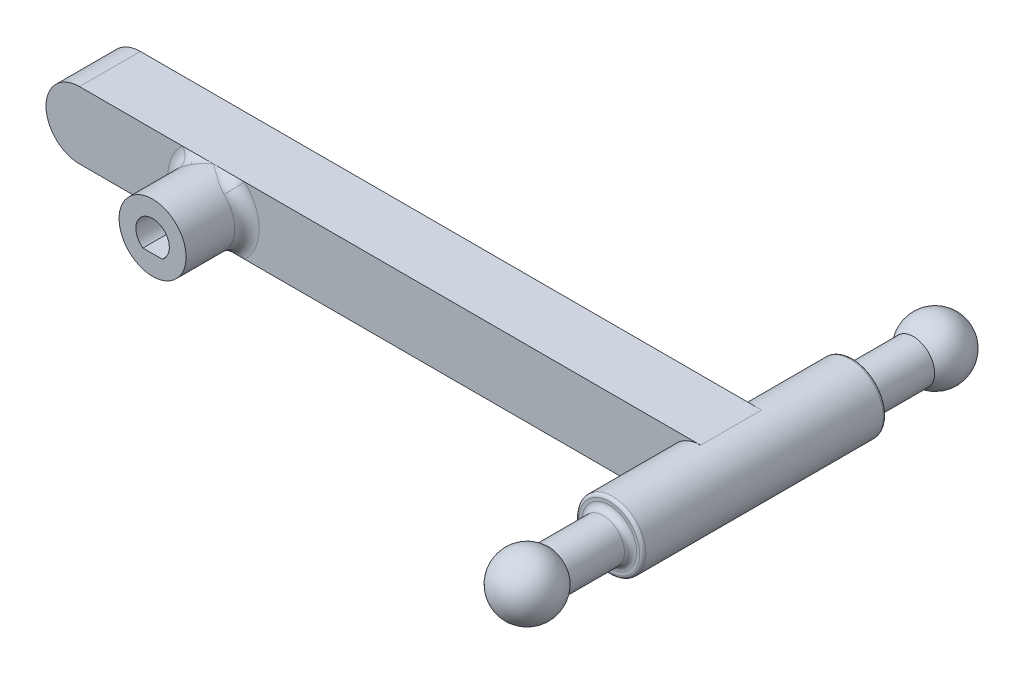
SolidWorks part; units mm, degrees
ref_plane "Front Plane" through (0, 0, 0) normal (0, 0, 1) x (1, 0, 0)
ref_plane "Top Plane" through (0, 0, 0) normal (0, 1, 0) x (1, 0, 0)
ref_plane "Right Plane" through (0, 0, 0) normal (1, 0, 0) x (0, 0, -1)
sketch "Sketch2" plane through (0, 0, 0) normal (0, 0, 1) x (1, 0, 0)
  line L0 (80, 0) -> (-42.1921, 0) construction
  line L2 (-22, -5.5) -> (80, -5.5)
  line L3 (80, -5.5) -> (80, 5.5)
  line L4 (0, 24.5757) -> (0, -40.5685) construction
  line L6 (-22, 5.5) -> (80, 5.5)
  line L7 (-1.5811, -2.25) -> (1.5811, -2.25)
  arc A0 (-22, 5.5) -> (-22, -5.5) centre (-22, 0) ccw
  arc A3 (1.5811, -2.25) -> (-1.5811, -2.25) centre (0, 0) ccw
  point P14 (0, 2.75)
  dimension "D1" = 5.5
  dimension "D5" = 2.75
  dimension "D2" = 80
  dimension "D3" = 22
  dimension "D4" = 5
extrude "Boss-Extrude2" add sketch "Sketch2" along normal mid plane 10
sketch "Sketch3" plane through (80, 0, 0) normal (1, 0, 0) x (0, 0, -1)
  line L0 (33.5, 0) -> (-33.5, 0) construction
  line L1 (-33.5, 0) -> (-33.5, 3.5)
  line L2 (-33.5, 3.5) -> (-21, 3.5)
  line L3 (-20, 4.5) -> (-20, 5)
  line L4 (-19.5, 5.5) -> (19.5, 5.5)
  line L5 (20, 5) -> (20, 4.5)
  line L6 (21, 3.5) -> (33.5, 3.5)
  line L7 (33.5, 3.5) -> (33.5, 0)
  line L8 (33.5, 0) -> (-33.5, 0)
  arc A0 (-21, 3.5) -> (-20, 4.5) centre (-21, 4.5) ccw
  arc A1 (20, 4.5) -> (21, 3.5) centre (21, 4.5) ccw
  arc A2 (-20, 5) -> (-19.5, 5.5) centre (-19.5, 5) cw
  arc A3 (19.5, 5.5) -> (20, 5) centre (19.5, 5) cw
  point P12 (20, 4.75)
  point P13 (0, 5.5)
  point P17 (-20, 5.5)
  point P20 (20, 5.5)
  dimension "D7" = 1
  dimension "D8" = 1
  dimension "D9" = 0.5
  dimension "D10" = 0.5
  dimension "D1" = 40
  dimension "D2" = 13.5
  dimension "D3" = 13.5
  dimension "D4" = 3.5
  dimension "D5" = 5.5
  dimension "D6" = 3.5
revolve "Revolve12" add sketch "Sketch3" angle 360 about L0
sketch "Sketch5" plane through (0, 0, -33.5) normal (0, 0, -1) x (-1, 0, 0)
  line L0 (-80, 5) -> (-80, -5) construction
  line L1 (-80, 5) -> (-80, -5)
  circle A0 centre (-80, 0) radius 5 construction
  arc A1 (-80, 5) -> (-80, -5) centre (-80, 0) ccw
revolve "Revolve16" add sketch "Sketch5" angle 360 about L0
sketch "Sketch6" plane through (0, 0, 33.5) normal (0, 0, 1) x (1, 0, 0)
  line L0 (80, 5) -> (80, -5) construction
  line L1 (80, 5) -> (80, -5)
  circle A0 centre (80, 0) radius 5 construction
  arc A1 (80, 5) -> (80, -5) centre (80, 0) ccw
revolve "Revolve17" add sketch "Sketch6" angle 360 about L0
sketch "Sketch8" plane through (0, 0, 5) normal (0, 0, 1) x (1, 0, 0)
  line L0 (-1.5811, -2.25) -> (1.5811, -2.25)
  circle A0 centre (0, 0) radius 5.5
  arc A1 (1.5811, -2.25) -> (-1.5811, -2.25) centre (0, 0) ccw
  point P6 (0, 2.75)
  dimension "D1" = 2.75
  dimension "D2" = 2.75
  dimension "D3" = 5
extrude "Boss-Extrude5" add sketch "Sketch8" along normal mid plane 20
fillet "Fillet1" radius 2 2 edges at (-5.5, 0, 5) (5.5, 0, 5)
sketch "Sketch9" plane through (0, -2.25, 0) normal (0, 1, 0) x (1, 0, 0)
  line L0 (0, -15) -> (0, -5) construction
  line L1 (-5.5, -15) -> (5.5, -15) construction
  circle A0 centre (0, -10) radius 1.5
  dimension "D1" = 3
extrude "Cut-Extrude1" cut sketch "Sketch9" against normal blind 10
sketch "Sketch10" plane through (0, 5.5, 0) normal (0, 1, 0) x (1, 0, 0)
  line L0 (84.5, 20) -> (75.5, 20) construction
  line L1 (100.096, 40.1532) -> (53.8183, 40.1532)
  line L2 (100.096, 40.1532) -> (100.096, 20)
  line L3 (100.096, 20) -> (53.8183, 20)
  line L4 (53.8183, 40.1532) -> (53.8183, 20)
  line L5 (114.0912, -20) -> (54.9379, -20)
  line L6 (114.0912, -20) -> (114.0912, -45.1915)
  line L7 (114.0912, -45.1915) -> (54.9379, -45.1915)
  line L8 (54.9379, -20) -> (54.9379, -45.1915)
  line L9 (75, -20) -> (85, -20) construction
sketch "Sketch11" plane through (0, 0, 20) normal (0, 0, 1) x (1, 0, 0)
  line L0 (82.2185, 1.625) -> (82.2185, -1.625)
  arc A0 (82.2185, 1.625) -> (82.2185, -1.625) centre (80, 0) ccw
  dimension "D1" = 5.5
  dimension "D2" = 3.25
